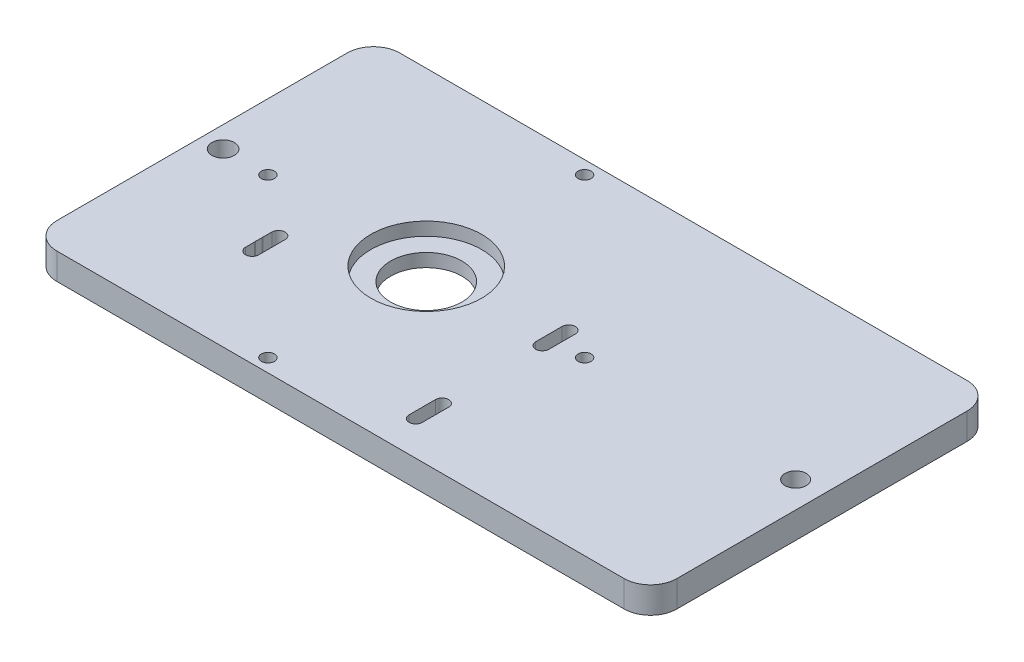
SolidWorks part; units mm, degrees
ref_plane "Front Plane" through (0, 0, 0) normal (0, 0, 1) x (1, 0, 0)
ref_plane "Top Plane" through (0, 0, 0) normal (0, 1, 0) x (1, 0, 0)
ref_plane "Right Plane" through (0, 0, 0) normal (1, 0, 0) x (0, 0, -1)
sketch "Sketch1" plane through (0, 0, 0) normal (0, 1, 0) x (1, 0, 0)
  line L0 (-38, -24.25) -> (-38, -21.75) construction
  line L5 (0, 55) -> (0, 65) construction
  line L6 (-75, 0) -> (150, 0) construction
  line L7 (-40.525, -24.25) -> (-40.525, -21.75)
  line L8 (-35.475, -24.25) -> (-35.475, -21.75)
  line L12 (0, 65) -> (150, 65)
  line L13 (150, 65) -> (150, -65)
  line L14 (150, -65) -> (0, -65)
  line L15 (-38, -23) -> (38, -23) construction
  line L16 (38, -23) -> (150, -23) construction
  line L17 (48, 65) -> (48, -65) construction
  line L19 (53, -55) -> (43, -55) construction
  line L20 (53, -55) -> (53, 9) construction
  line L21 (53, 9) -> (43, 9) construction
  line L22 (43, -55) -> (43, 9) construction
  line L23 (53, -55) -> (43, 9) construction
  line L24 (53, 9) -> (43, -55) construction
  line L25 (48, -52) -> (48, -42) construction
  line L26 (45.5, -52) -> (45.5, -42)
  line L27 (50.5, -52) -> (50.5, -42)
  line L28 (48, 6) -> (48, -4) construction
  line L29 (45.5, 6) -> (45.5, -4)
  line L30 (50.5, 6) -> (50.5, -4)
  line L34 (0, 0) -> (0, -23) construction
  line L35 (-38, -18) -> (-38, -28) construction
  line L36 (-40.5, -18) -> (-40.5, -28)
  line L37 (-35.5, -18) -> (-35.5, -28)
  line L39 (0, 65) -> (-85, 65)
  line L41 (0, -65) -> (-85, -65)
  line L42 (-85, 65) -> (-85, -65)
  circle A0 centre (0, 0) radius 21
  arc A5 (-40.525, -24.25) -> (-35.475, -24.25) centre (-38, -24.25) ccw
  arc A6 (-35.475, -21.75) -> (-40.525, -21.75) centre (-38, -21.75) ccw
  circle A10 centre (0, 0) radius 13.5
  arc A11 (0, 65) -> (0, -65) centre (0, 0) ccw
  arc A12 (0, -65) -> (0, 65) centre (0, 0) ccw
  arc A13 (0, 55) -> (0, -55) centre (0, 0) ccw
  arc A14 (0, -55) -> (0, 55) centre (0, 0) ccw
  circle A15 centre (0, 60) radius 2.475
  circle A21 centre (48, 1) radius 2.5
  circle A22 centre (48, -47) radius 2.5
  circle A23 centre (60, 0) radius 2.475
  circle A24 centre (0, -60) radius 2.475
  circle A25 centre (-60, 0) radius 2.475
  arc A27 (45.5, -52) -> (50.5, -52) centre (48, -52) ccw
  arc A28 (50.5, -42) -> (45.5, -42) centre (48, -42) ccw
  arc A29 (45.5, 6) -> (50.5, 6) centre (48, 6) cw
  arc A30 (50.5, -4) -> (45.5, -4) centre (48, -4) cw
  arc A33 (-40.5, -18) -> (-35.5, -18) centre (-38, -18) cw
  arc A34 (-35.5, -28) -> (-40.5, -28) centre (-38, -28) cw
  circle A35 centre (140, 0) radius 4.025
  circle A37 centre (-77, 0) radius 4.25
  point P0 (0, 0)
  point P10 (-38, -23)
  point P39 (1, 1)
  point P47 (48, -23)
  point P58 (0, 0)
  point P60 (48, -47)
  point P67 (48, 1)
  point P82 (-38, -23)
  dimension "D3" = 42
  dimension "D7" = 2.525
  dimension "D8" = 150
  dimension "D13" = 27
  dimension "D14" = 65
  dimension "D15" = 4.95
  dimension "D19" = 8.05
  dimension "D20" = 10
  dimension "D24" = 5
  dimension "D27" = 5
  dimension "D31" = 8.5
  dimension "D2" = 10
  dimension "D6" = 2.5
  dimension "D9" = 23
  dimension "D11" = 38
  dimension "D21" = 102
  dimension "D22" = 64
  dimension "D23" = 10
  dimension "D25" = 8
  dimension "D26" = 85
  dimension "D28" = 10
  dimension "D32" = 8
  dimension "D16" = 4
extrude "Boss-Extrude1" add sketch "Sketch1" along normal blind 10 contours A12 L14 L13 L12 A21 A22 | A11 A12 A23 A15 A14 A13 | A13 A14 A24 A6 L8 A5 L7 A0 region at (57.0663, 0, -27.0705) region at (99.5045, 0, -0.1944) region at (53.4444, 0, 0)
extrude "Boss-Extrude4" add sketch "Sketch1<5>" along normal blind 10 contours A11 L39 L42 L41 A37 region at (-66.5532, 0, 0)
sketch "Sketch1<5>" plane through (0, 0, 0) normal (0, 1, 0) x (1, 0, 0) same geometry as "Sketch1"
extrude "Boss-Extrude2" add sketch "Sketch1<4>" along normal blind 5 contours A0 A10 region at (-20.406, 0, 0)
sketch "Sketch1<4>" plane through (0, 0, 0) normal (0, 1, 0) x (1, 0, 0) same geometry as "Sketch1"
fillet "Fillet1" radius 10 4 edges at (150, 5, 65) (150, 5, -65) (-85, 5, -65) (-85, 5, 65)
